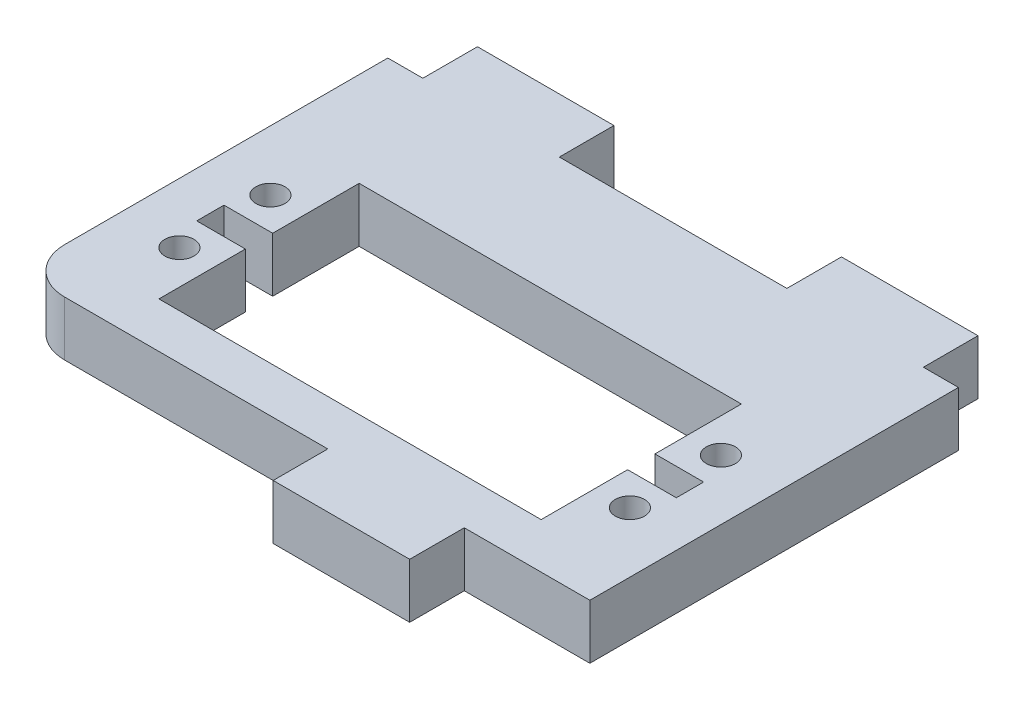
SolidWorks part; units mm, degrees
ref_plane "Plano frontal" through (0, 0, 0) normal (0, 0, 1) x (1, 0, 0)
ref_plane "Plano superior" through (0, 0, 0) normal (0, 1, 0) x (1, 0, 0)
ref_plane "Plano direito" through (0, 0, 0) normal (1, 0, 0) x (0, 0, -1)
ref_plane "Plano1" through (0, -6, 0) normal (0, -1, 0) x (1, 0, 0)
sketch "Esboço1" plane through (0, -6, 0) normal (0, -1, 0) x (1, 0, 0)
  line L0 (-26.35, 1.5) -> (-21, 1.5)
  line L1 (-21, 1.5) -> (-21, 11)
  line L2 (-21, 11) -> (21, 11)
  line L3 (21, 11) -> (21, 1.5)
  line L4 (21, 1.5) -> (26.35, 1.5)
  line L5 (26.35, 1.5) -> (26.35, -1.5)
  line L6 (26.35, -1.5) -> (21, -1.5)
  line L7 (21, -1.5) -> (21, -11)
  line L8 (21, -11) -> (-21, -11)
  line L9 (-21, -11) -> (-21, -1.5)
  line L10 (-21, -1.5) -> (-26.35, -1.5)
  line L11 (-26.35, -1.5) -> (-26.35, 1.5)
  line L12 (2.5526, 16) -> (-26.35, 16)
  line L13 (-31.35, 11) -> (-31.35, -24.5)
  line L14 (-31.35, -24.5) -> (-27.5, -24.5)
  line L15 (-27.5, -24.5) -> (-27.5, -30.5)
  line L16 (-27.5, -30.5) -> (-12.5, -30.5)
  line L17 (-12.5, -30.5) -> (-12.5, -24.5)
  line L18 (-12.5, -24.5) -> (12.5, -24.5)
  line L19 (12.5, -24.5) -> (12.5, -30.5)
  line L20 (12.5, -30.5) -> (27.5, -30.5)
  line L21 (27.5, -30.5) -> (27.5, -24.5)
  line L22 (27.5, -24.5) -> (31.35, -24.5)
  line L23 (31.35, -24.5) -> (31.35, 16)
  line L24 (31.35, 16) -> (17.5526, 16)
  line L25 (17.5526, 16) -> (17.5526, 22)
  line L26 (17.5526, 22) -> (2.5526, 22)
  line L27 (2.5526, 22) -> (2.5526, 16)
  line L28 (-24.75, 5) -> (24.75, -5) construction
  line L29 (21, 11) -> (-21, -11) construction
  circle A0 centre (24.75, 5) radius 1.6
  circle A1 centre (24.75, -5) radius 1.6
  circle A2 centre (-24.75, 5) radius 1.6
  circle A3 centre (-24.75, -5) radius 1.6
  arc A4 (-26.35, 16) -> (-31.35, 11) centre (-26.35, 11) ccw
  point P38 (0, 0)
  point P39 (0, 0)
  point P40 (0, 0)
  point P41 (0, 0)
  point P42 (0, 0)
  point P43 (0, 0)
  point P44 (0, 0)
  point P45 (0, 0)
  point P46 (0, -24.5)
  point P47 (0, 0)
  point P48 (0, 0)
  point P49 (0, 0)
  point P50 (10.0526, 22)
  point P51 (0, 0)
  point P52 (0, 0)
  point P53 (26.35, 0)
  point P54 (-26.35, 0)
  dimension "D10" = 3.2
  dimension "D11" = 6.6
  dimension "D13" = 5
  dimension "D1" = 40.5
  dimension "D2" = 62.7
  dimension "D3" = 6
  dimension "D4" = 25
  dimension "D5" = 42
  dimension "D6" = 22
  dimension "D7" = 49.5
  dimension "D8" = 10
  dimension "D9" = 15
  dimension "D12" = 5
  dimension "D14" = 10.0526
  dimension "D15" = 3
  dimension "D16" = 1.6
extrude "Ressalto-extrusão1" add sketch "Esboço1" against normal blind 6
